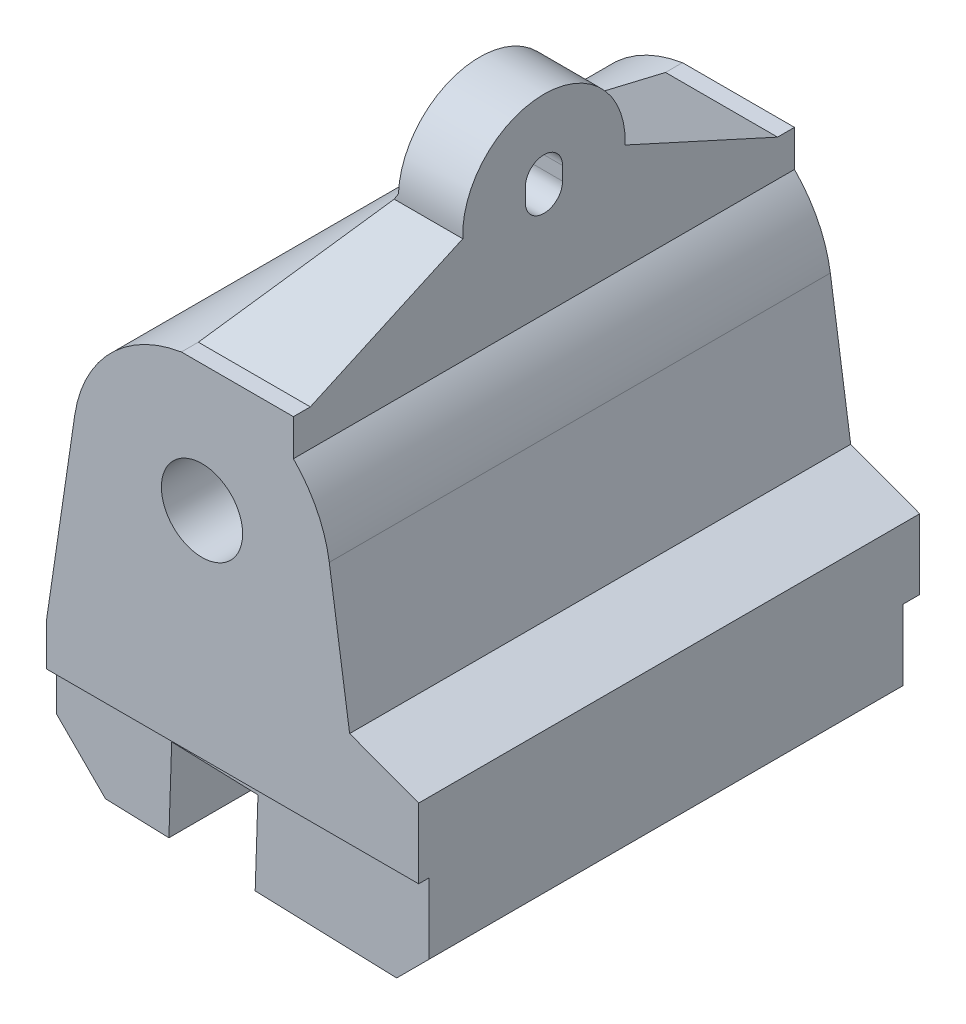
SolidWorks part; units mm, degrees
ref_plane "前视基准面" through (0, 0, 0) normal (0, 0, 1) x (1, 0, 0)
ref_plane "上视基准面" through (0, 0, 0) normal (0, 1, 0) x (1, 0, 0)
ref_plane "右视基准面" through (0, 0, 0) normal (1, 0, 0) x (0, 0, -1)
sketch "草图1" plane through (0, 0, 0) normal (0, 0, 1) x (1, 0, 0)
  line L0 (-92, -103) -> (-75.1879, 11.0805)
  line L1 (-92, -103) -> (-92, -153)
  line L2 (-92, -153) -> (-63, -182)
  line L3 (-63, -182) -> (-25.5545, -183.2345)
  line L4 (-25.5545, -183.2345) -> (-23.9079, -133.2846)
  line L5 (-23.9079, -133.2846) -> (27.0645, -134.965)
  line L6 (27.0645, -134.965) -> (25.4178, -184.9149)
  line L7 (25.4178, -184.9149) -> (109, -187.6703)
  line L8 (109, -187.6703) -> (128, -168.6703)
  line L9 (128, -168.6703) -> (128, -85.6703)
  line L10 (128, -85.6703) -> (32, -50) construction
  line L11 (75.1879, 11.0805) -> (92, -103) construction
  line L12 (0, 0) -> (0, -182) construction
  line L13 (-63, -182) -> (167.1773, -182) construction
  line L14 (-25.5545, -183.2345) -> (25.4178, -184.9149) construction
  line L15 (0, -182) -> (6, 0) construction
  line L16 (-63, -182) -> (-63, 0) construction
  line L17 (-63, -182) -> (-57, 0) construction
  line L18 (0, 0) -> (-116.977, 0) construction
  line L19 (0, 0) -> (32, 0) construction
  line L20 (0, -50) -> (32, -50) construction
  line L21 (0, -50) -> (-116.977, -50) construction
  line L22 (75.1879, 11.0805) -> (87.2127, -70.5152)
  line L23 (87.2127, -70.5152) -> (128, -85.6703)
  circle A0 centre (0, 0) radius 24 construction
  arc A1 (-58.5956, -48.4) -> (-57.2364, -50) centre (0, 0) ccw
  arc A2 (0, -76) -> (3.4972, -75.9195) centre (0, 0) ccw
  arc A3 (75.1879, 11.0805) -> (-76, 0) centre (0, 0) ccw
  point P16 (6, 0)
  point P20 (-0.0684, -182)
  point P33 (-0.0684, -184.0747)
  point P34 (0, -184.9149)
  dimension "D1" = 48
  dimension "D2" = 152
  dimension "D3" = 182
  dimension "D4" = 45
  dimension "D5" = 29
  dimension "D6" = 79
  dimension "D7" = 92
  dimension "D8" = 220
  dimension "D9" = 45
  dimension "D10" = 134
  dimension "D11" = 6
  dimension "D12" = 6
  dimension "D13" = 25.5
  dimension "D14" = 51
  dimension "D15" = 19
  dimension "D16" = 102
  dimension "D18" = 32
  dimension "D17" = 50
extrude "凸台-拉伸1" add sketch "草图1" along normal blind 296 contours L22 A3 L0 L1 L2 L3 L4 L5 L6 L7 L8 L9 L23 region at (10.9362, -66.0561, 0)
sketch "草图2" plane through (0, 0, 296) normal (0, 0, 1) x (1, 0, 0)
  circle A0 centre (0, 0) radius 24
  dimension "D1" = 48
extrude "切除-拉伸1" cut sketch "草图2" against normal up to next
sketch "草图3" plane through (0, 0, 296) normal (0, 0, 1) x (1, 0, 0)
  line L0 (54, 53.479) -> (54, 166)
  line L1 (54, 166) -> (16, 166)
  line L2 (16, 166) -> (16, 120)
  line L3 (16, 120) -> (-25, 54.5436) construction
  line L4 (16, 120) -> (-12.1751, 75.0184)
  arc A0 (75.1879, 11.0805) -> (-75.1879, 11.0805) centre (0, 0) ccw construction
  arc A1 (54, 53.479) -> (-12.1751, 75.0184) centre (0, 0) ccw
  circle A2 centre (0, 0) radius 60 construction
  dimension "D5" = 120
  dimension "D1" = 348
  dimension "D2" = 54
  dimension "D3" = 38
  dimension "D4" = 120
  dimension "D6" = 41
extrude "凸台-拉伸2" add sketch "草图3" against normal up to surface (296 mm away) up to face at (24, 0, 0)
sketch "草图4" plane through (16, 0, 0) normal (-1, 0, 0) x (0, 0, 1)
  line L0 (148, 166) -> (148, -244.5055) construction
  line L1 (0, 166) -> (296, 166) construction
  line L3 (296, 24) -> (0, 24) construction
  line L4 (296, 24) -> (0, 24) construction
  line L5 (0, -24) -> (296, -24) construction
  line L6 (0, -24) -> (296, -24) construction
  line L7 (247.7162, 24) -> (247.7162, -24) construction
  line L8 (247.7162, 0) -> (364.965, 0) construction
  line L9 (148, 124) -> (148, 116) construction
  line L10 (159, 124) -> (159, 116)
  line L11 (137, 124) -> (137, 116)
  line L12 (0, 120) -> (296, 120) construction
  arc A0 (159, 124) -> (137, 124) centre (148, 124) ccw
  arc A1 (137, 116) -> (159, 116) centre (148, 116) ccw
  point P15 (148, 120)
  dimension "D1" = 11
  dimension "D2" = 30
extrude "切除-拉伸2" cut sketch "草图4" against normal up to next and the other way up to next
sketch "草图5" plane through (16, 0, 0) normal (-1, 0, 0) x (0, 0, 1)
  line L0 (137, 120) -> (159, 120) construction
  circle A0 centre (148, 120) radius 38
  dimension "D1" = 76
extrude "切除-拉伸4" cut sketch "草图5" against normal blind 16 and the other way up to next
sketch "草图6" plane through (16, 0, 0) normal (-1, 0, 0) x (0, 0, 1)
  line L0 (296, 75.0184) -> (286, 75.0184)
  line L1 (0, 75.0184) -> (296, 75.0184) construction
  line L2 (286, 75.0184) -> (195.9583, 116)
  line L3 (100.0417, 116) -> (10, 75.0184)
  line L4 (10, 75.0184) -> (0, 75.0184)
  line L6 (0, -24) -> (296, -24) construction
  line L7 (0, -24) -> (296, -24) construction
  line L8 (296, 24) -> (0, 24) construction
  line L9 (296, 24) -> (0, 24) construction
  line L10 (148, 24) -> (148, -24) construction
  line L11 (148, 0) -> (407.4993, 0) construction
  line L12 (0, 166) -> (296, 166) construction
  line L14 (0, 75.0184) -> (0, 166)
  line L15 (0, 166) -> (148, 166)
  line L16 (148, 166) -> (296, 166)
  line L17 (296, 166) -> (296, 75.0184)
  arc A1 (195.9583, 116) -> (100.0417, 116) centre (148, 118) ccw
  line M11 (0, 120) -> (110, 120)
  line M13 (186, 120) -> (296, 120)
  line M14 (296, 120) -> (296, 166)
  line M15 (296, 166) -> (0, 166)
  line M16 (0, 166) -> (0, 120)
  dimension "D4" = 96
  dimension "D1" = 10
  dimension "D2" = 10
  dimension "D3" = 116
extrude "切除-拉伸10" cut sketch "草图6" against normal up to next contours A1 M13 M14 M15 region at (16, 144.1918, 240.1069)
extrude "切除-拉伸11" cut sketch "草图6<5>" against normal up to next contours A1 M15 M16 M11 region at (16, 144.1918, 55.8931)
sketch "草图6<5>" plane through (16, 0, 0) normal (-1, 0, 0) x (0, 0, 1) same geometry as "草图6"
extrude "切除-拉伸12" cut sketch "草图6<6>" against normal up to next and the other way up to next contours A1 L14 L4 L3 M11 | A1 L2 L0 L17 M13 region at (16, 103.645, 259.8851) region at (16, 103.645, 36.1149)
sketch "草图6<6>" plane through (16, 0, 0) normal (-1, 0, 0) x (0, 0, 1) same geometry as "草图6"
sketch "草图10" plane through (0, 0, 296) normal (0, 0, 1) x (1, 0, 0)
  line L0 (-141.0758, -127) -> (212.4784, -127)
  dimension "D1" = 127
extrude "切除-拉伸-薄壁1" cut sketch "草图10" against normal blind 6 and the other way through all flip side to cut thin thin type one direction wall 70
sketch "草图11" plane through (0, 0, 0) normal (0, 0, -1) x (-1, 0, 0)
  line L0 (-166.219, -127) -> (149.1003, -127)
  dimension "D1" = 127
extrude "切除-拉伸-薄壁2" cut sketch "草图11" against normal blind 10 and the other way through all thin thin type one direction wall 70
sketch "草图12" plane through (-6.0619, -183.8771, 0) normal (-0.0329, -0.9995, 0) x (0.9995, -0.0329, 0)
  line L0 (31.4967, 10) -> (115.1244, 10) construction
  line L1 (31.4967, 290) -> (-19.5033, 290) construction
  line L2 (31.4967, 262.5) -> (87.8436, 79.6571)
  line L3 (31.4967, 290) -> (31.4967, 10) construction
  line L4 (31.4967, 85.9319) -> (38.1498, 64.3429)
  line L5 (31.4967, 290) -> (31.4967, 10) construction
  line L6 (5.9967, 290) -> (5.9967, 10) construction
  line L7 (-19.5033, 10) -> (31.4967, 10) construction
  line L9 (31.4967, 262.5) -> (31.4967, 85.9319)
  arc A0 (38.1498, 64.3429) -> (87.8436, 79.6571) centre (62.9967, 72) ccw
  point P6 (5.9967, 290)
  dimension "D3" = 52
  dimension "D1" = 62
  dimension "D2" = 57
  dimension "D4" = 190.5
extrude "切除-拉伸13" cut sketch "草图12" against normal up to surface (49.977 mm away) up to face at (1.5783, -134.1248, 150)
ref_plane "基准面1" through (-6.0619, -183.8771, 0) normal (-0.0329, -0.9995, 0) x (-0.9995, 0.0329, 0)
